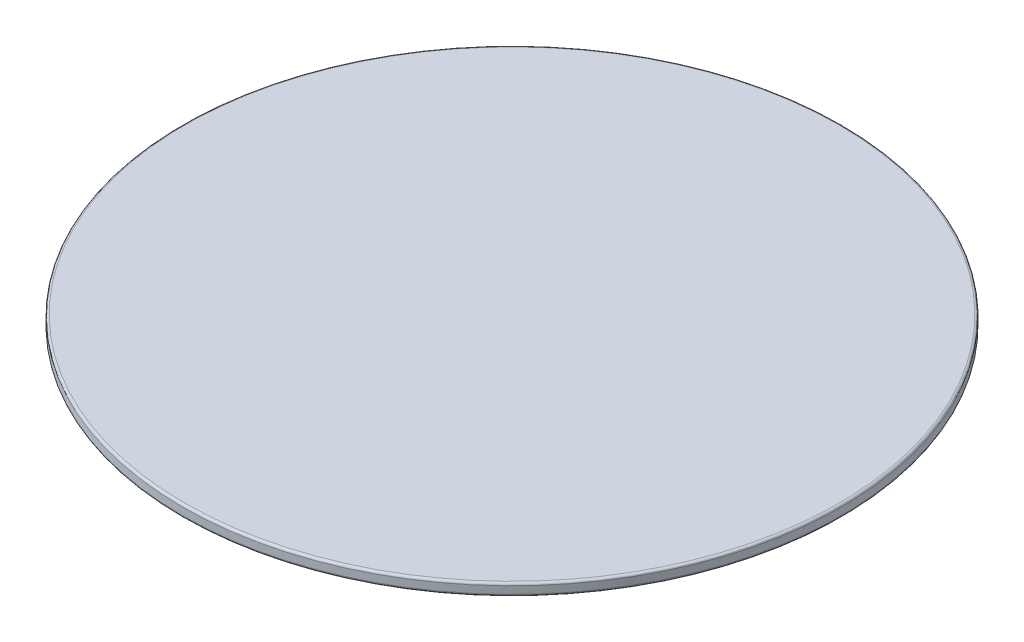
SolidWorks part; units mm, degrees
ref_plane "Front Plane" through (0, 0, 0) normal (0, 0, 1) x (1, 0, 0)
ref_plane "Top Plane" through (0, 0, 0) normal (0, 1, 0) x (1, 0, 0)
ref_plane "Right Plane" through (0, 0, 0) normal (1, 0, 0) x (0, 0, -1)
sketch "Sketch1" plane through (0, 0, 0) normal (0, 1, 0) x (1, 0, 0)
  circle A0 centre (0, 0) radius 145
  dimension "D1" = 290
extrude "Boss-Extrude1" add sketch "Sketch1" along normal blind 5.25
fillet "Fillet1" radius 1 2 edges at (0, 5.25, 145) (0, 0, 145)
